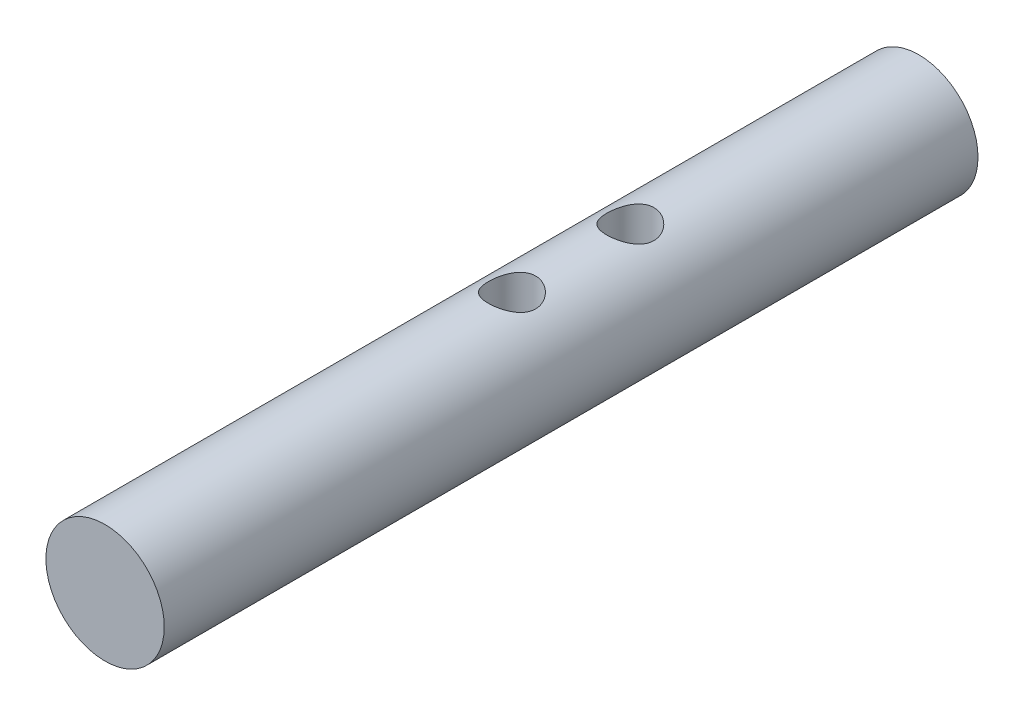
SolidWorks part; units mm, degrees
material "6061 合金"
ref_plane "正面" through (0, 0, 0) normal (0, 0, 1) x (1, 0, 0)
ref_plane "平面" through (0, 0, 0) normal (0, 1, 0) x (1, 0, 0)
ref_plane "右側面" through (0, 0, 0) normal (1, 0, 0) x (0, 0, -1)
sketch "断面" plane through (0, 0, 0) normal (0, 0, 1) x (1, 0, 0)
  circle A0 centre (0, 0) radius 4
  dimension "D1" = 8
extrude "軸全長" add sketch "断面" along normal blind 55
ref_axis "中心軸" through (0, 0, 55) along (0, 0, -1)
ref_plane "上面" through (0, 4, 0) normal (0, 1, 0) x (1, 0, 0)
sketch "上面穴スケッチ" plane through (0, 4, 0) normal (0, 1, 0) x (1, 0, 0)
  line L0 (0, -55) -> (0, 0) construction
  line L1 (4, 0) -> (-4, 0) construction
  circle A0 centre (0, -19.5) radius 1.6
  circle A1 centre (0, -27.5) radius 1.6
  dimension "D1" = 19.5
  dimension "D2" = 3.2
  dimension "D3" = 8
extrude "上面穴貫通" cut sketch "上面穴スケッチ" against normal through all
sketch "上面キー溝スケッチ" plane through (0, 4, 0) normal (0, 1, 0) x (1, 0, 0)
  line L0 (0, -30) -> (0, -50) construction
  line L1 (0, -55) -> (0, 0) construction
  line L2 (1.5, -30) -> (1.5, -50)
  line L3 (-1.5, -30) -> (-1.5, -50)
  line L4 (4, 0) -> (-4, 0) construction
  arc A0 (1.5, -30) -> (-1.5, -30) centre (0, -30) ccw
  arc A1 (-1.5, -50) -> (1.5, -50) centre (0, -50) ccw
  point P5 (0, -40)
  dimension "D1" = 3
  dimension "D2" = 30
  dimension "D3" = 20
extrude "上面キー溝1.6mm" [suppressed] cut sketch "上面キー溝スケッチ" against normal blind 1.6
sketch "上面Dカットスケッチ" plane through (0, 4, 0) normal (0, 1, 0) x (1, 0, 0)
  line L0 (-4, 0) -> (-4, -55) construction
  line L1 (4, -55) -> (-4, -55)
  line L2 (4, -55) -> (4, -45)
  line L3 (4, -45) -> (-4, -45)
  line L4 (-4, -55) -> (-4, -45)
  dimension "D1" = 10
extrude "上面Dカット1mm" [suppressed] cut sketch "上面Dカットスケッチ" against normal blind 1
sketch "Eリング溝スケッチ" plane through (0, 0, 0) normal (0, 1, 0) x (1, 0, 0)
  line L0 (4, -55) -> (4, 0) construction
  line L1 (4, -1) -> (3, -1)
  line L2 (4, -1) -> (4, -2)
  line L3 (4, -2) -> (3, -2)
  line L4 (3, -1) -> (3, -2)
  line L5 (4, 0) -> (-4, 0) construction
  dimension "D1" = 1
  dimension "D2" = 1
revolve "Eリング溝カット" [suppressed] cut sketch "Eリング溝スケッチ" angle 360 about axis through (0, 0, 55) along (0, 0, -1)
